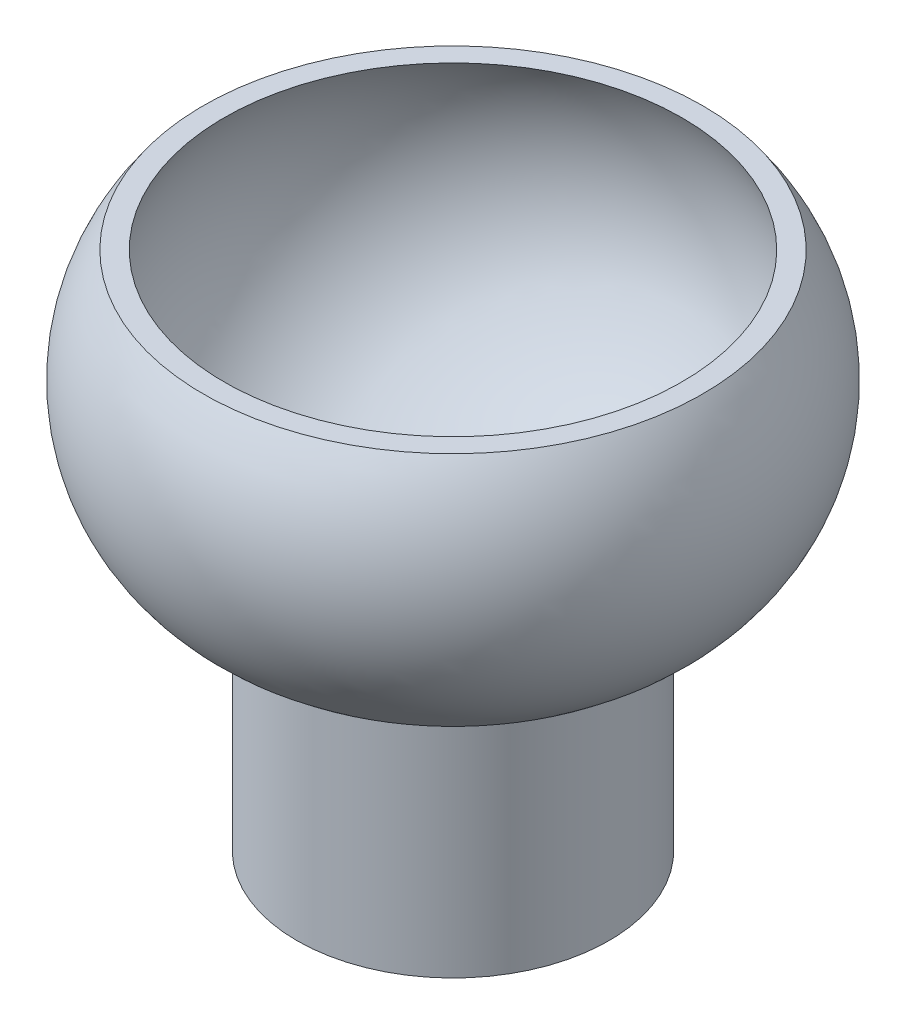
SolidWorks part; units mm, degrees
ref_plane "Front Plane" through (0, 0, 0) normal (0, 0, 1) x (1, 0, 0)
ref_plane "Top Plane" through (0, 0, 0) normal (0, 1, 0) x (1, 0, 0)
ref_plane "Right Plane" through (0, 0, 0) normal (1, 0, 0) x (0, 0, -1)
sketch "Sketch2" plane through (0, 0, 0) normal (0, 0, 1) x (1, 0, 0)
  line L0 (0, 0) -> (0, 12.7)
  line L1 (0, -6.985) -> (0, 6.985) construction
  line L2 (0, 12.7) -> (6.096, 12.7)
  line L3 (0, 0) -> (3.81, 0)
  line L4 (3.8582, 0) -> (-3.8582, 0) construction
  line L5 (3.81, 0) -> (3.81, 5.588)
  arc A0 (6.096, 12.7) -> (3.81, 5.588) centre (2.4429, 9.9508) cw
  arc A1 (5.588, 12.7) -> (0, 6.35) centre (1.7537, 10.4404) cw
  point P11 (5.588, 12.7)
  point P12 (0, 5.842)
  point P13 (0, 6.35)
  dimension "D4" = 5.588
  dimension "D5" = 4.572
  dimension "D8" = 4.4505
  dimension "D1" = 12.7
  dimension "D2" = 6.096
  dimension "D3" = 3.81
  dimension "D6" = 0.508
  dimension "D7" = 0.508
revolve "Revolve2" add sketch "Sketch2" angle 360 about L0 region at (2.7726, 4.305, 0)
